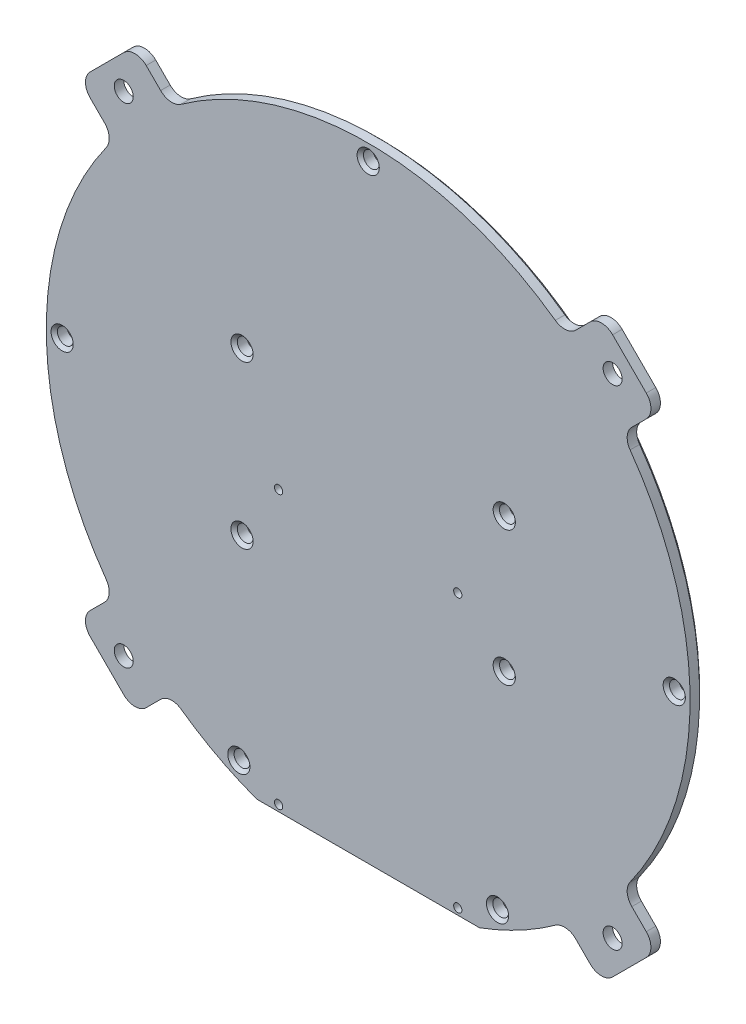
SolidWorks part; units mm, degrees
ref_plane "Plano frontal" through (0, 0, 0) normal (0, 0, 1) x (1, 0, 0)
ref_plane "Plano superior" through (0, 0, 0) normal (0, 1, 0) x (1, 0, 0)
ref_plane "Plano direito" through (0, 0, 0) normal (1, 0, 0) x (0, 0, -1)
sketch "Esboço1" plane through (0, 0, 0) normal (0, 0, 1) x (1, 0, 0)
  line L0 (-30.5, -95.2352) -> (-35.107, -95.2352)
  line L1 (-35.107, -95.2352) -> (-30.5, -95.2352) construction
  line L2 (-35.107, -95.2352) -> (35.107, -95.2352)
  line L3 (-30.5, -4.7352) -> (-30.5, -95.2352) construction
  line L4 (30.5, -4.7352) -> (-30.5, -4.7352) construction
  line L5 (30.5, -95.2352) -> (30.5, -4.7352) construction
  line L6 (-30.5, -4.7352) -> (-30.5, -95.2352)
  line L7 (30.5, -4.7352) -> (-30.5, -4.7352)
  line L8 (30.5, -95.2352) -> (30.5, -4.7352)
  arc A0 (35.107, -95.2352) -> (-35.107, -95.2352) centre (0, 0) ccw
  circle A1 centre (-40.7827, -87.4587) radius 2.5 construction
  circle A2 centre (-96.5, 0) radius 2.5 construction
  circle A3 centre (-39.7861, -25.4579) radius 2.5 construction
  circle A4 centre (-39.7861, 25.6051) radius 2.5 construction
  circle A5 centre (0, 96.5) radius 2.5 construction
  circle A6 centre (42.9049, 21.1182) radius 2.5 construction
  circle A7 centre (96.5, 0) radius 2.5 construction
  circle A8 centre (42.9049, -21.3079) radius 2.5 construction
  circle A9 centre (40.7827, -87.4587) radius 2.5 construction
  circle A10 centre (-40.7827, -87.4587) radius 2.5
  circle A11 centre (-96.5, 0) radius 2.5
  circle A12 centre (-39.7861, -25.4579) radius 2.5
  circle A13 centre (-39.7861, 25.6051) radius 2.5
  circle A14 centre (0, 96.5) radius 2.5
  circle A15 centre (42.9049, 21.1182) radius 2.5
  circle A16 centre (96.5, 0) radius 2.5
  circle A17 centre (42.9049, -21.3079) radius 2.5
  circle A18 centre (40.7827, -87.4587) radius 2.5
  circle A19 centre (28.25, -93.2352) radius 1.3
  circle A20 centre (-28.25, -93.2352) radius 1.3
  circle A21 centre (-28.25, -7.2352) radius 1.3
  circle A22 centre (28.25, -7.2352) radius 1.3
  dimension "D1" = 203
  dimension "D2" = 2.6
extrude "Ressalto-extrusão1" add sketch "Esboço1" along normal blind 4 contours L2 A0 L0 L6 L7 L8 A18 A17 A16 A15 A14 A13 A12 A11 A10 | L2 L8 L7 L6 A22 A21 A20 A19 region at (0, -49.9843, 0) region at (-0.0046, 11.6152, 0)
extrude "Corte-extrusão3" cut sketch "Esboço1<4>" along normal blind 1.5 contours L2 L8 L7 L6 A22 A21 A20 A19 region at (0, -49.9843, 0)
sketch "Esboço1<4>" plane through (0, 0, 0) normal (0, 0, 1) x (1, 0, 0) same geometry as "Esboço1"
sketch "Esboço2" plane through (0, 0, 4) normal (0, 0, 1) x (1, 0, 0)
  line L0 (0, 95.2352) -> (0, -95.2352) construction
  line L1 (-35.107, -95.2352) -> (35.107, -95.2352) construction
  line L2 (-101.5, 0) -> (101.5, 0) construction
  line L3 (0, 0) -> (71.7713, -71.7713) construction
  line L4 (71.7713, -71.7713) -> (82.3779, -82.3779) construction
  line L5 (82.3779, -82.3779) -> (87.6812, -77.0746)
  line L6 (87.6812, -70.0036) -> (83.1221, -65.4444)
  line L7 (77.0746, -87.6812) -> (82.3779, -82.3779)
  line L8 (70.0036, -87.6812) -> (65.4444, -83.1221)
  line L9 (-82.3779, -82.3779) -> (-77.0746, -87.6812)
  line L10 (-70.0036, -87.6812) -> (-65.4444, -83.1221)
  line L11 (-87.6812, -77.0746) -> (-82.3779, -82.3779)
  line L12 (-87.6812, -70.0036) -> (-83.1221, -65.4444)
  line L13 (-71.7713, -71.7713) -> (-82.3779, -82.3779) construction
  line L14 (-82.3779, 82.3779) -> (-87.6812, 77.0746)
  line L15 (-87.6812, 70.0036) -> (-83.1221, 65.4444)
  line L16 (-77.0746, 87.6812) -> (-82.3779, 82.3779)
  line L17 (-70.0036, 87.6812) -> (-65.4444, 83.1221)
  line L18 (-71.7713, 71.7713) -> (-82.3779, 82.3779) construction
  line L19 (82.3779, 82.3779) -> (77.0746, 87.6812)
  line L20 (70.0036, 87.6812) -> (65.4444, 83.1221)
  line L21 (87.6812, 77.0746) -> (82.3779, 82.3779)
  line L22 (87.6812, 70.0036) -> (83.1221, 65.4444)
  line L23 (71.7713, 71.7713) -> (82.3779, 82.3779) construction
  line L24 (-82.5892, -59.0024) -> (-59.0024, -82.5892)
  line L25 (-82.5892, 59.0024) -> (-59.0024, 82.5892)
  line L26 (82.5892, 59.0024) -> (59.0024, 82.5892)
  line L27 (59.0024, -82.5892) -> (82.5892, -59.0024)
  arc A0 (35.107, -95.2352) -> (-35.107, -95.2352) centre (0, 0) ccw construction
  arc A1 (35.107, -95.2352) -> (59.0024, -82.5892) centre (0, 0) ccw
  arc A2 (77.0746, -87.6812) -> (70.0036, -87.6812) centre (73.5391, -84.1457) cw
  arc A3 (87.6812, -77.0746) -> (87.6812, -70.0036) centre (84.1457, -73.5391) ccw
  arc A4 (59.0024, -82.5892) -> (65.4444, -83.1221) centre (61.9089, -86.6576) cw
  arc A6 (82.5892, -59.0024) -> (83.1221, -65.4444) centre (86.6576, -61.9089) ccw
  circle A7 centre (77.0746, -77.0746) radius 3
  arc A8 (35.107, -95.2352) -> (-35.107, -95.2352) centre (0, 0) ccw
  arc A9 (-87.6812, -77.0746) -> (-87.6812, -70.0036) centre (-84.1457, -73.5391) cw
  arc A10 (-77.0746, -87.6812) -> (-70.0036, -87.6812) centre (-73.5391, -84.1457) ccw
  arc A11 (-82.5892, -59.0024) -> (-83.1221, -65.4444) centre (-86.6576, -61.9089) cw
  arc A12 (-59.0024, -82.5892) -> (-65.4444, -83.1221) centre (-61.9089, -86.6576) ccw
  circle A13 centre (-77.0746, -77.0746) radius 3
  arc A14 (-77.0746, 87.6812) -> (-70.0036, 87.6812) centre (-73.5391, 84.1457) cw
  arc A15 (-87.6812, 77.0746) -> (-87.6812, 70.0036) centre (-84.1457, 73.5391) ccw
  arc A16 (-59.0024, 82.5892) -> (-65.4444, 83.1221) centre (-61.9089, 86.6576) cw
  arc A17 (-82.5892, 59.0024) -> (-83.1221, 65.4444) centre (-86.6576, 61.9089) ccw
  circle A18 centre (-77.0746, 77.0746) radius 3
  arc A19 (87.6812, 77.0746) -> (87.6812, 70.0036) centre (84.1457, 73.5391) cw
  arc A20 (77.0746, 87.6812) -> (70.0036, 87.6812) centre (73.5391, 84.1457) ccw
  arc A21 (82.5892, 59.0024) -> (83.1221, 65.4444) centre (86.6576, 61.9089) cw
  arc A22 (59.0024, 82.5892) -> (65.4444, 83.1221) centre (61.9089, 86.6576) ccw
  circle A23 centre (77.0746, 77.0746) radius 3
  point P6 (0, 0)
  point P14 (0, 0)
  point P81 (0, 0)
  arc M10 (35.107, -95.2352) -> (-35.107, -95.2352) centre (0, 0) ccw
  dimension "D5" = 5
  dimension "D4" = 5
  dimension "D8" = 4
  dimension "D1" = 45
  dimension "D2" = 180
  dimension "D3" = 25
  dimension "D6" = 15
  dimension "D7" = 7.5
extrude "Ressalto-extrusão3" add sketch "Esboço2" against normal blind 3 contours A12 A11 L12 A9 L11 L9 A10 L10 A13 M10 | A17 A16 L17 A14 L16 L14 A15 L15 A18 M10 | A22 A21 L22 A19 L21 L19 A20 L20 A23 M10 | A6 A4 L8 A2 L7 L5 A3 L6 A7 M10 region at (79.4249, -84.7282, 4) region at (-72.0728, -72.0728, 4) region at (-72.0728, 72.0728, 4) region at (72.0728, 72.0728, 4)
chamfer "Chanfro1" distance 1 angle 45 3 edges at (-32.8035, -95.2352, 0) (32.8035, -95.2352, 0) (0, 101.5, 0)
chamfer "Chanfro2" distance 1 angle 45 9 edges at (43.2827, -87.4587, 4) (-38.2827, -87.4587, 4) (2.5, 96.5, 4) (-94, 0, 4) (99, 0, 4) (45.4049, 21.1182, 4) (45.4049, -21.3079, 4) (-37.2861, -25.4579, 4) (-37.2861, 25.6051, 4)
